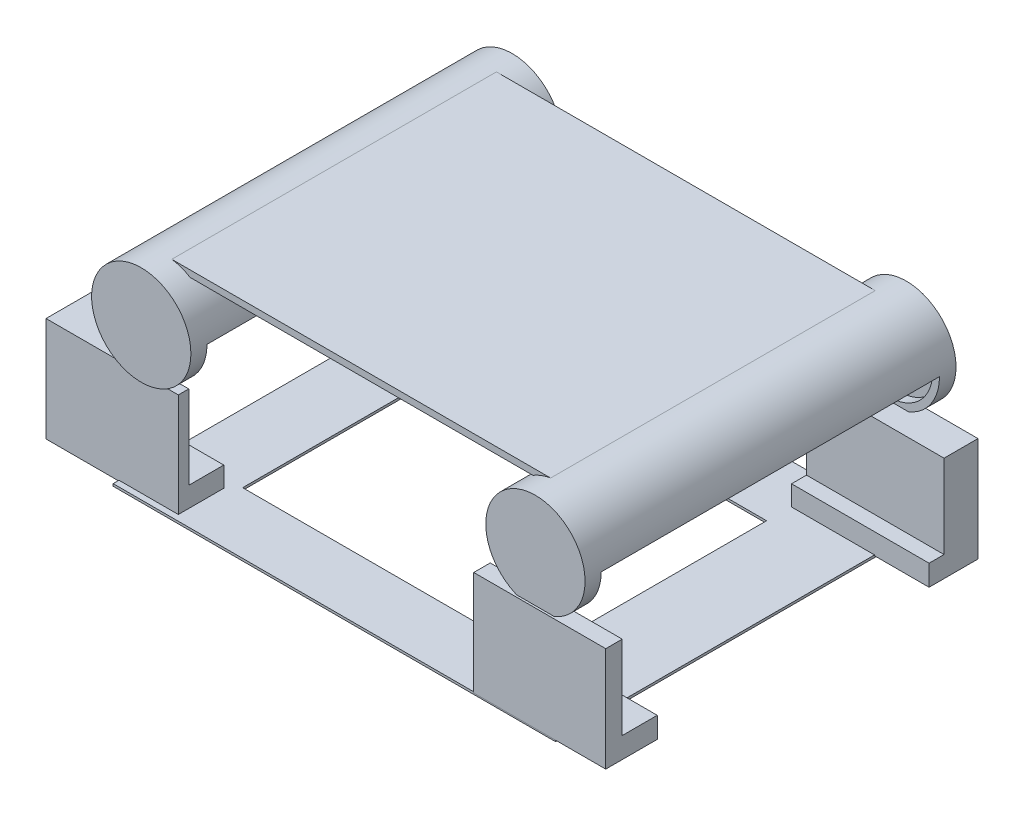
SolidWorks part; units mm, degrees
ref_plane "Front Plane" through (0, 0, 0) normal (0, 0, 1) x (1, 0, 0)
ref_plane "Top Plane" through (0, 0, 0) normal (0, 1, 0) x (1, 0, 0)
ref_plane "Right Plane" through (0, 0, 0) normal (1, 0, 0) x (0, 0, -1)
sketch "MotorHoldersSketch" plane through (0, 0, 0) normal (0, 0, 1) x (1, 0, 0)
  line L0 (0, 0) -> (170, 0) construction
  line L1 (0, 0) -> (0, 21.41) construction
  line L2 (170, 0) -> (170, 21.41) construction
  circle A0 centre (0, 0) radius 21.41
  circle A1 centre (170, 0) radius 21.41
ref_axis "Axis1" through (0, 0, 0) along (0, 0, 1)
ref_axis "Axis2" through (170, 0, 0) along (0, 0, 1)
extrude "MotorHolders" add sketch "MotorHoldersSketch" along normal blind 80 and the other way blind 80
sketch "Sketch3" plane through (0, 0, 0) normal (0, 0, 1) x (1, 0, 0)
  line L1 (1.9406, 21.133) -> (168.3435, 21.133)
  line L2 (1.9406, 21.133) -> (1.9406, 18.3155)
  line L3 (1.9406, 18.3155) -> (168.3435, 18.3155)
  line L4 (168.3435, 21.133) -> (168.3435, 18.3155)
extrude "Boss-Extrude2" add sketch "Sketch3" along normal blind 70 and the other way blind 70
sketch "Sketch4" plane through (0, 0, 0) normal (0, 1, 0) x (1, 0, 0)
  line L1 (221.2811, -73.0508) -> (-41.4939, -73.0508)
  line L2 (221.2811, -73.0508) -> (221.2811, 72.8691)
  line L3 (221.2811, 72.8691) -> (-41.4939, 72.8691)
  line L4 (-41.4939, -73.0508) -> (-41.4939, 72.8691)
extrude "Cut-Extrude1" cut sketch "Sketch4" against normal blind 23
sketch "MotorHolderExtrudeSketch" plane through (0, 0, 0) normal (0, 0, 1) x (1, 0, 0)
  circle A0 centre (170, 0) radius 18.415
  circle A1 centre (0, 0) radius 18.415
  circle A3 centre (0, 0) radius 21.41 construction
  circle A4 centre (170, 0) radius 21.41 construction
extrude "MotorHolderExtrude" cut sketch "MotorHolderExtrudeSketch" against normal blind 77 and the other way blind 77
ref_axis "Axis3" through (170, 0, 0) along (0, -1, 0)
sketch3d "3DSketch1"
  line L0 (170, 0, 0) -> (170, -34.8293, 0)
  line L1 (170, 0, 0) -> (170, -38.994, 0) construction
ref_plane "Plane1" through (170, -34.8293, 0) normal (0, -1, 0) x (-1, 0, 0)
sketch "Sketch6" plane through (170, -34.8293, 0) normal (0, -1, 0) x (-1, 0, 0)
  line L1 (208.9484, 78.949) -> (154.5717, 78.949)
  line L2 (208.9484, 78.949) -> (208.9484, 56.3099)
  line L3 (208.9484, 56.3099) -> (154.5717, 56.3099)
  line L4 (154.5717, 78.949) -> (154.5717, 56.3099)
  line L5 (212.8011, -58.6712) -> (155.7267, -58.6712)
  line L6 (212.8011, -58.6712) -> (212.8011, -78.2822)
  line L7 (212.8011, -78.2822) -> (155.7267, -78.2822)
  line L8 (155.7267, -58.6712) -> (155.7267, -78.2822)
  line L9 (26.2975, 77.8627) -> (-33.0241, 77.8627)
  line L10 (26.2975, 77.8627) -> (26.2975, 56.7633)
  line L11 (26.2975, 56.7633) -> (-33.0241, 56.7633)
  line L12 (-33.0241, 77.8627) -> (-33.0241, 56.7633)
  line L13 (25.701, -58.6712) -> (-31.2222, -58.6712)
  line L14 (25.701, -58.6712) -> (25.701, -80.8954)
  line L15 (25.701, -80.8954) -> (-31.2222, -80.8954)
  line L16 (-31.2222, -58.6712) -> (-31.2222, -80.8954)
extrude "PowerBankHolders" add sketch "Sketch6" along normal blind 30 and the other way blind 15 separate body
sketch3d "3DSketch3"
  line L0 (170, 0, 0) -> (170, -64.5, 0) construction
  point P3 (0, 0, 0)
ref_plane "Plane2" through (170, -64.5, 0) normal (0, -1, 0) x (-1, 0, 0)
sketch "Sketch7" plane through (170, -64.5, 0) normal (0, -1, 0) x (-1, 0, 0)
  line L1 (-9.5047, -80.801) -> (181.32, -80.801)
  line L2 (-9.5047, -80.801) -> (-9.5047, 73.8662)
  line L3 (-9.5047, 73.8662) -> (181.32, 73.8662)
  line L4 (181.32, -80.801) -> (181.32, 73.8662)
  line L5 (151.8712, -54.3972) -> (26.5361, -54.3972)
  line L6 (151.8712, -54.3972) -> (151.8712, 46.2413)
  line L7 (151.8712, 46.2413) -> (26.5361, 46.2413)
  line L8 (26.5361, -54.3972) -> (26.5361, 46.2413)
extrude "TopCellPhoneCover" add sketch "Sketch7" along normal blind 1
sketch "Sketch9" plane through (170, -34.8293, 0) normal (0, -1, 0) x (-1, 0, 0)
  line L1 (183.1646, -73.7814) -> (-59.9818, -73.7814)
  line L2 (183.1646, -73.7814) -> (183.1646, 63.2186)
  line L3 (183.1646, 63.2186) -> (-59.9818, 63.2186)
  line L4 (-59.9818, -73.7814) -> (-59.9818, 63.2186)
extrude "Cut-Extrude3" cut sketch "Sketch9" along normal blind 21 and the other way blind 21
